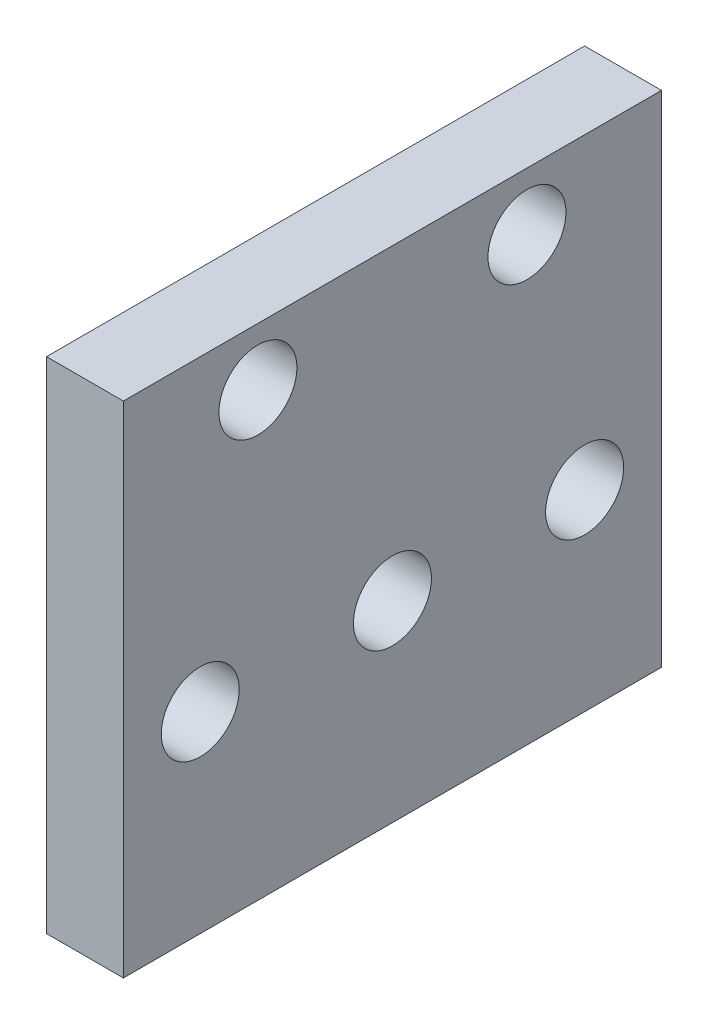
SolidWorks part; units mm, degrees
ref_plane "Front" through (0, 0, 0) normal (0, 0, 1) x (1, 0, 0)
ref_plane "Top" through (0, 0, 0) normal (0, 1, 0) x (1, 0, 0)
ref_plane "Right" through (0, 0, 0) normal (1, 0, 0) x (0, 0, -1)
sketch "Sketch1" plane through (0, 0, 0) normal (1, 0, 0) x (0, 0, -1)
  line L1 (-17.78, -16.51) -> (17.78, -16.51)
  line L2 (-17.78, -16.51) -> (-17.78, 16.51)
  line L3 (-17.78, 16.51) -> (17.78, 16.51)
  line L4 (17.78, -16.51) -> (17.78, 16.51)
  line L5 (-17.78, -16.51) -> (17.78, 16.51) construction
  line L6 (-17.78, 16.51) -> (17.78, -16.51) construction
  point P0 (0, 0)
  dimension "D1" = 35.56
  dimension "D2" = 33.02
extrude "Boss-Extrude1" add sketch "Sketch1" along normal blind 5.08
sketch "Sketch2" plane through (5.08, 0, 0) normal (1, 0, 0) x (0, 0, -1)
  line L0 (-17.78, 8.89) -> (17.78, 8.89) construction
  line L1 (-17.78, 16.51) -> (-17.78, -16.51) construction
  line L2 (17.78, -16.51) -> (17.78, 16.51) construction
  line L3 (-17.78, -16.51) -> (17.78, -16.51) construction
  line L4 (0, 8.89) -> (0, 16.51) construction
  line L5 (17.78, 16.51) -> (-17.78, 16.51) construction
  line L6 (0, 12.7) -> (-17.78, 12.7) construction
  line L7 (0, 12.7) -> (17.78, 12.7) construction
  line L8 (0, 8.89) -> (0, -16.51) construction
  line L9 (-12.7, -3.81) -> (12.7, -3.81) construction
  circle A0 centre (-8.89, 12.7) radius 2.5781
  circle A1 centre (8.89, 12.7) radius 2.5781
  circle A2 centre (-12.7, -3.81) radius 2.5781
  circle A3 centre (0, -3.81) radius 2.5781
  circle A4 centre (12.7, -3.81) radius 2.5781
  point P23 (0, -3.81)
  dimension "D2" = 5.1562
  dimension "D3" = 5.1562
  dimension "D5" = 5.1562
  dimension "D1" = 25.4
  dimension "D4" = 25.4
extrude "Cut-Extrude1" cut sketch "Sketch2" against normal through all
